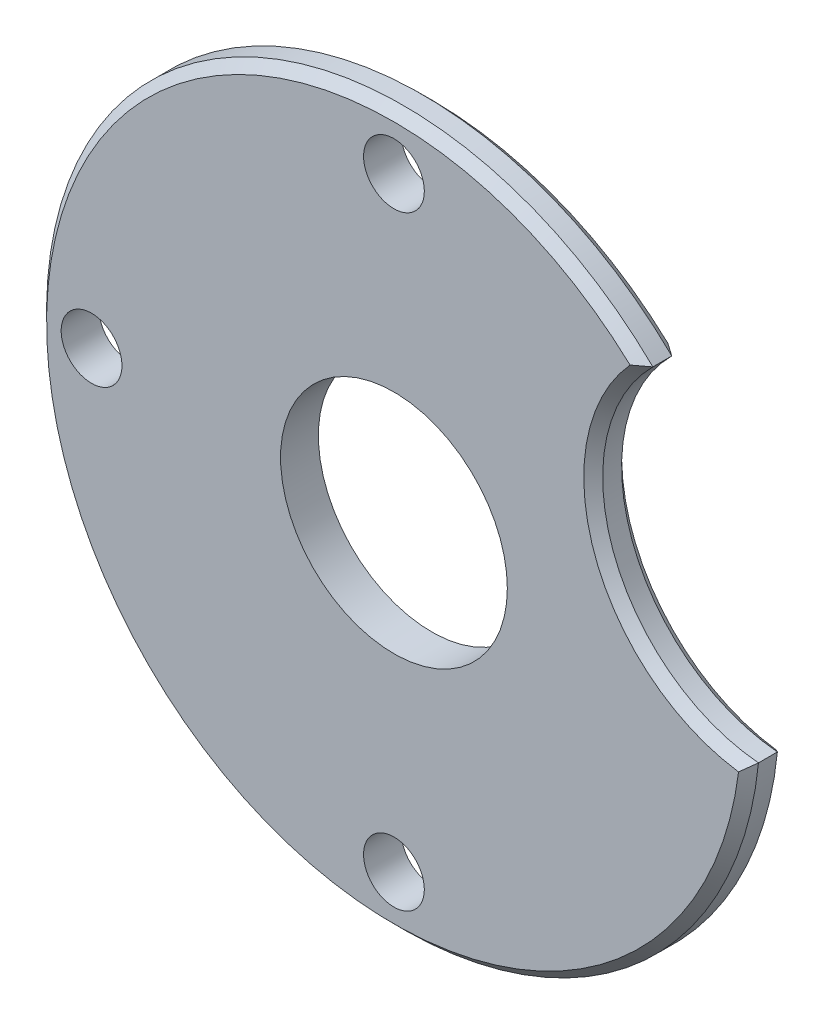
SolidWorks part; units mm, degrees
material "Nylon 101"
ref_plane "Front Plane" through (0, 0, 0) normal (0, 0, 1) x (1, 0, 0)
ref_plane "Top Plane" through (0, 0, 0) normal (0, 1, 0) x (1, 0, 0)
ref_plane "Right Plane" through (0, 0, 0) normal (1, 0, 0) x (0, 0, -1)
sketch "Sketch1" plane through (0, 0, 0) normal (0, 0, 1) x (1, 0, 0)
  line L0 (0, 0) -> (31.0287, 11.2935) construction
  line L1 (0, 25.4) -> (0, 0) construction
  circle A0 centre (0, 0) radius 29.972
  circle A1 centre (31.0287, 11.2935) radius 14.2875
  circle A2 centre (0, 0) radius 9.525
  circle A3 centre (0, 0) radius 25.4 construction
  circle A4 centre (0, 25.4) radius 2.5527
  circle A5 centre (-25.4, 0) radius 2.5527
  circle A6 centre (0, -25.4) radius 2.5527
  dimension "D1" = 59.944
  dimension "D3" = 28.575
  dimension "D4" = 19.05
  dimension "D5" = 50.8
  dimension "D6" = 5.1054
  dimension "D7" = 5.1054
  dimension "D8" = 5.1054
  dimension "D2" = 33.02
  dimension "D9" = 70
extrude "Boss-Extrude1" add sketch "Sketch1" along normal blind 3.175 contours A1 A0 A6 A5 A4 A2 region at (16.8071, 6.1173, 0)
chamfer "Chamfer1" distance 0.7937 angle 45 2 edges at (17.6028, 6.4069, 3.175) (-28.1645, -10.251, 3.175)
chamfer "Chamfer2" distance 0.7937 angle 45 2 edges at (17.6028, 6.4069, 0) (-28.1645, -10.251, 0)
